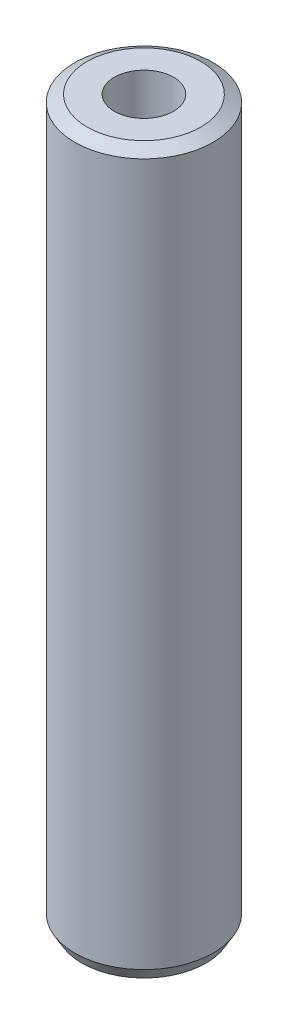
SolidWorks part; units mm, degrees
ref_plane "Front Plane" through (0, 0, 0) normal (0, 0, 1) x (1, 0, 0)
ref_plane "Top Plane" through (0, 0, 0) normal (0, 1, 0) x (1, 0, 0)
ref_plane "Right Plane" through (0, 0, 0) normal (1, 0, 0) x (0, 0, -1)
sketch "Sketch1" plane through (0, 0, 0) normal (0, 1, 0) x (1, 0, 0)
  circle A0 centre (0, 0) radius 57.5
  dimension "SHAFT_OD" = 115
extrude "Boss-Extrude1" add sketch "Sketch1" along normal blind 600
sketch "Sketch2" plane through (0, 0, 0) normal (0, 1, 0) x (1, 0, 0)
  circle A0 centre (0, 0) radius 24.6047
  dimension "BORE_D" = 49.2095
extrude "Cut-Extrude1" cut sketch "Sketch2" along normal through all
chamfer "Chamfer1" distance 5.8947 angle 60 2 edges at (0, 600, 57.5) (0, 0, 57.5) first distance on face at (0, 600, 57.5) first distance on face at (0, 0, 24.6047)
